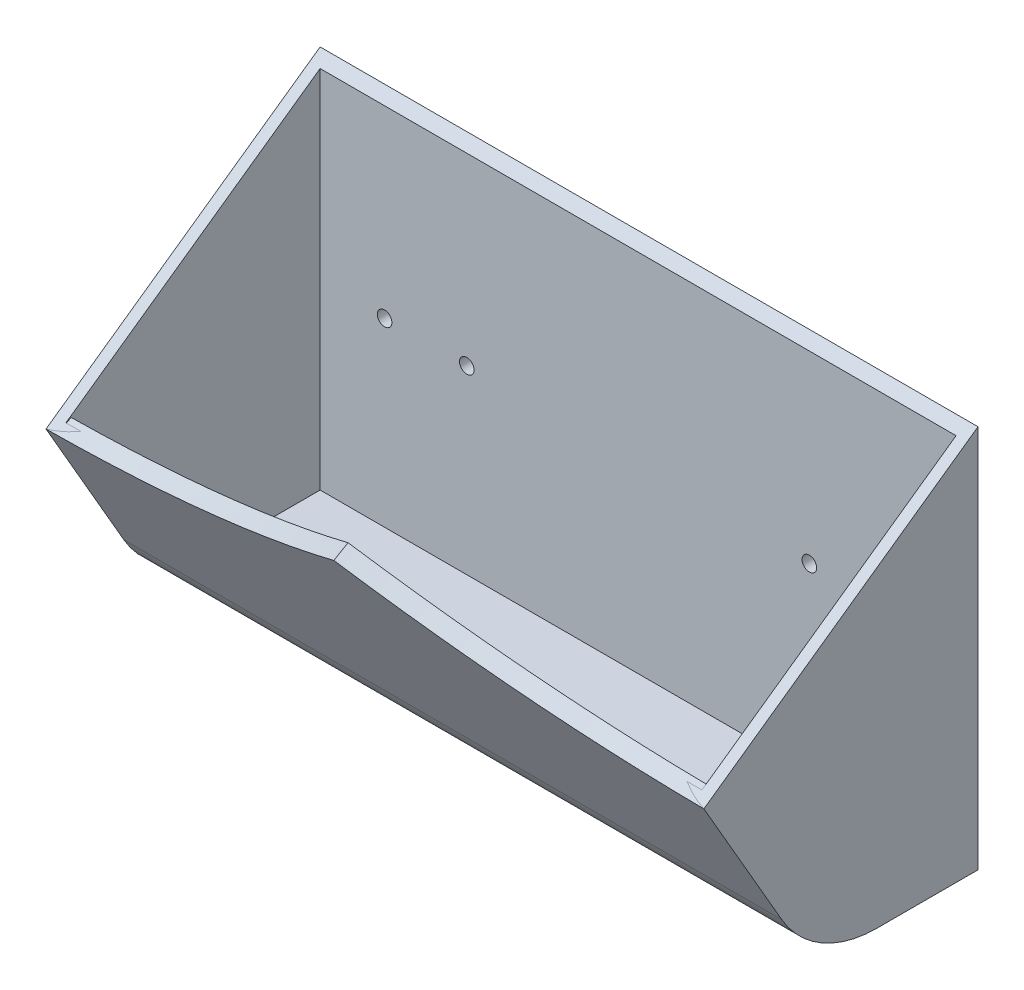
SolidWorks part; units mm, degrees
ref_plane "Front Plane" through (0, 0, 0) normal (0, 0, 1) x (1, 0, 0)
ref_plane "Top Plane" through (0, 0, 0) normal (0, 1, 0) x (1, 0, 0)
ref_plane "Right Plane" through (0, 0, 0) normal (1, 0, 0) x (0, 0, -1)
sketch "Sketch1" plane through (0, 0, 0) normal (0, 0, 1) x (1, 0, 0)
  line L1 (-76.2, 38.1) -> (76.2, 38.1)
  line L2 (-76.2, 38.1) -> (-76.2, -38.1)
  line L3 (-76.2, -38.1) -> (76.2, -38.1)
  line L4 (76.2, 38.1) -> (76.2, -38.1)
  line L5 (-76.2, 38.1) -> (76.2, -38.1) construction
  line L6 (-76.2, -38.1) -> (76.2, 38.1) construction
  point P0 (0, 0)
  dimension "D1" = 152.4
  dimension "D2" = 76.2
sketch "Sketch2" plane through (0, 0, 0) normal (1, 0, 0) x (0, 0, -1)
  line L0 (0, 50.8) -> (0, -38.1)
  line L1 (0, 38.1) -> (0, -38.1) construction
  line L2 (0, -38.1) -> (0, 38.1) construction
  line L3 (0, 38.1) -> (0, -38.1) construction
  line L4 (0, -38.1) -> (-38.1, -38.1)
  line L5 (-38.1, -38.1) -> (-63.5, 5.8941)
  line L6 (-63.5, 5.8941) -> (0, 50.8)
  dimension "D1" = 38.1
  dimension "D2" = 120
  dimension "D3" = 50.8
  dimension "D4" = 88.9
extrude "Boss-Extrude1" add sketch "Sketch2" along normal mid plane 152.4
fillet "Fillet1" radius 25.4 1 edges at (0, -38.1, 38.1)
sketch "Sketch3" plane through (0, -26.0228, 45.0728) normal (0, -0.5, 0.866) x (1, 0, 0)
  line L0 (-76.2, 32.9956) -> (-76.2, -32.9956) construction
  line L1 (76.2, 36.8544) -> (-76.2, 36.8544) construction
  line L2 (-76.2, 36.8544) -> (76.2, 36.8544)
  arc A0 (-76.2, 36.8544) -> (0, 55.9044) centre (-80.1577, 214.6104) ccw
  arc A1 (0, 55.9044) -> (76.2, 36.8544) centre (80.1577, 214.6104) ccw
  dimension "D2" = 177.8
  dimension "D3" = 177.8
  dimension "D1" = 19.05
  dimension "D4" = 76.2
ref_plane "Plane1" through (0, -26.0228, 45.0728) normal (0, -0.5, 0.866) x (1, 0, 0)
shell "Shell1" thickness 2.54 removed face at (0, 28.347, 31.75)
extrude "Boss-Extrude4" add sketch "Sketch3" against normal blind 3.81
sketch "Sketch5" plane through (0, 0, 0) normal (0, 0, -1) x (-1, 0, 0)
  line L0 (0, 0) -> (-76.2, 0) construction
  line L1 (-76.2, -38.1) -> (-76.2, 50.8) construction
  line L2 (0, 0) -> (76.2, 0) construction
  line L3 (76.2, -38.1) -> (76.2, 50.8) construction
  line L4 (-76.2, 6.35) -> (76.2, 6.35) construction
  line L5 (-76.2, 50.8) -> (-76.2, -38.1) construction
  line L6 (-76.2, 50.8) -> (76.2, 50.8) construction
  line L7 (-76.2, -38.1) -> (76.2, -38.1) construction
  line L8 (68.58, 50.8) -> (68.58, -38.1) construction
  line L9 (-76.2, 15.875) -> (-76.2, -3.175)
  line L10 (-76.2, -3.175) -> (-50.8, -3.175)
  line L11 (-50.8, -3.175) -> (-50.8, 15.875)
  line L12 (-50.8, 15.875) -> (-76.2, 15.875)
  line L17 (0, 0) -> (0, 50.8)
  line L18 (0, 50.8) -> (0, -38.1)
  line L19 (-63.5, 15.875) -> (-63.5, -3.175) construction
  line L20 (50.8, -3.175) -> (50.8, 15.875)
  line L21 (76.2, -3.175) -> (50.8, -3.175)
  line L22 (76.2, 15.875) -> (76.2, -3.175)
  line L23 (50.8, 15.875) -> (76.2, 15.875)
  circle A0 centre (-68.58, 10.795) radius 2.54
  circle A1 centre (-57.15, 10.795) radius 2.54
  circle A2 centre (-57.15, 1.905) radius 2.54
  circle A3 centre (-68.58, 1.905) radius 2.54
  circle A4 centre (57.15, 1.905) radius 2.54
  circle A5 centre (68.58, 1.905) radius 2.54
  circle A6 centre (68.58, 10.795) radius 2.54
  circle A7 centre (57.15, 10.795) radius 2.54
  dimension "D9" = 5.08
  dimension "D10" = 5.08
  dimension "D13" = 5.08
  dimension "D14" = 5.08
  dimension "D1" = 6.35
  dimension "D2" = 0
  dimension "D3" = 7.62
  dimension "D4" = 19.05
  dimension "D5" = 25.4
  dimension "D6" = 9.525
  dimension "D11" = 6.35
  dimension "D12" = 6.35
  dimension "D15" = 5.08
  dimension "D16" = 5.08
  dimension "D17" = 5.08
  dimension "D18" = 5.08
  dimension "D19" = 7.62
  dimension "D20" = 7.62
sketch "Sketch6" plane through (0, 0, 0) normal (0, 0, -1) x (-1, 0, 0)
  line L0 (-76.2, 6.35) -> (76.2, 6.35) construction
  line L1 (-76.2, -38.1) -> (-76.2, 50.8) construction
  line L2 (76.2, -38.1) -> (76.2, 50.8) construction
  line L3 (-76.2, 10.3124) -> (76.2, 10.3124)
  line L4 (-76.2, 2.3876) -> (76.2, 2.3876)
  line L5 (-34.8996, 10.3124) -> (-34.8996, 2.3876)
  line L6 (34.8996, 10.3124) -> (34.8996, 2.3876)
  line L7 (-58.7248, 6.35) -> (-39.6748, 6.35)
  line L8 (39.6748, 6.35) -> (58.7248, 6.35)
  circle A0 centre (-58.7248, 6.35) radius 1.6891
  circle A1 centre (-39.6748, 6.35) radius 1.6891
  circle A2 centre (39.6748, 6.35) radius 1.6891
  circle A3 centre (58.7248, 6.35) radius 1.6891
  dimension "D10" = 3.3782
  dimension "D11" = 3.3782
  dimension "D12" = 3.3782
  dimension "D13" = 3.3782
  dimension "D1" = 6.35
  dimension "D2" = 3.9624
  dimension "D3" = 3.9624
  dimension "D4" = 41.3004
  dimension "D5" = 41.3004
  dimension "D6" = 17.4752
  dimension "D7" = 4.7752
  dimension "D8" = 4.7752
  dimension "D9" = 17.4752
extrude "Cut-Extrude2" cut sketch "Sketch6" against normal up to next contours A0 | A1 | A2 | A3
